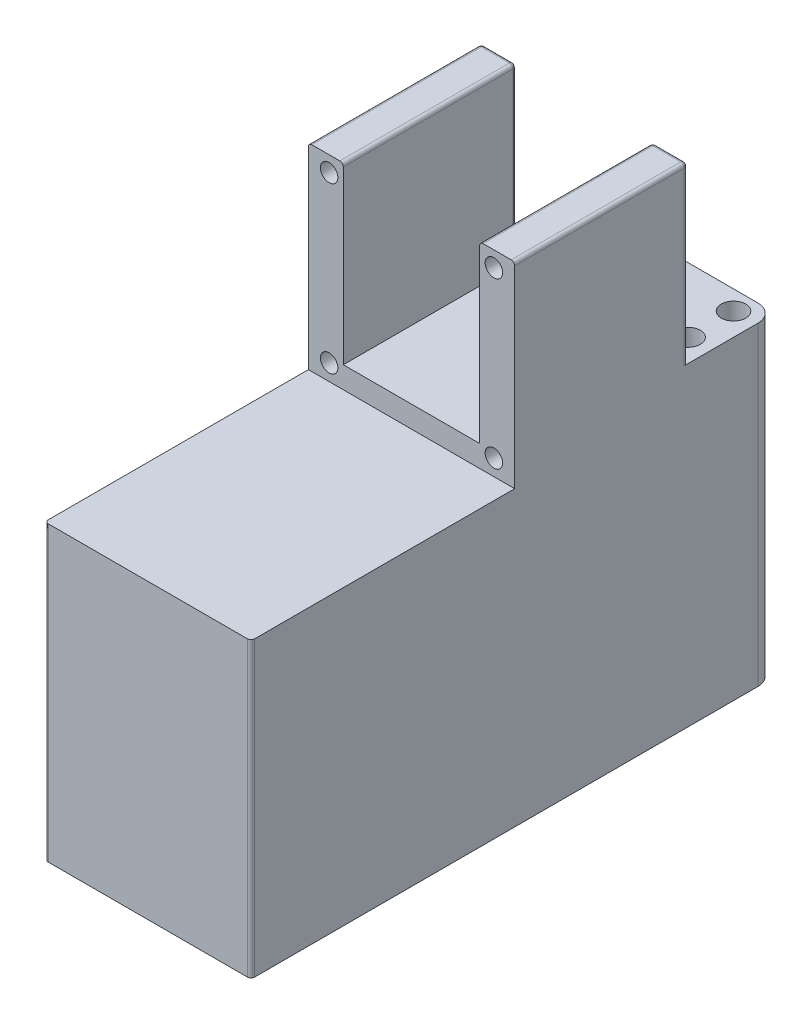
SolidWorks part; units mm, degrees
note: The reader was unsure of these and kept them because the rebuilt part matched: shared geometry of "Sketch6<3>".
ref_plane "Front Plane" through (0, 0, 0) normal (0, 0, 1) x (1, 0, 0)
ref_plane "Top Plane" through (0, 0, 0) normal (0, 1, 0) x (1, 0, 0)
ref_plane "Right Plane" through (0, 0, 0) normal (1, 0, 0) x (0, 0, -1)
sketch "Sketch1" plane through (0, 0, 0) normal (0, 0, 1) x (1, 0, 0)
  line L1 (-29.5, 15) -> (29.5, 15)
  line L2 (-29.5, 15) -> (-29.5, -15)
  line L3 (-29.5, -15) -> (29.5, -15)
  line L4 (29.5, 15) -> (29.5, -15)
  line L5 (-29.5, 15) -> (29.5, -15) construction
  line L6 (-29.5, -15) -> (29.5, 15) construction
  line L90 (4, 2.7272) -> (6.5728, 5.3)
  line L91 (6.5728, 5.3) -> (8, 5.3)
  line L92 (8, 5.3) -> (8, 3.1)
  line L93 (8, 3.1) -> (10, 5.1)
  line L94 (10, 5.1) -> (10, 10)
  line L95 (10, 10) -> (5.1, 10)
  line L96 (5.1, 10) -> (3.1, 8)
  line L97 (3.1, 8) -> (5.3, 8)
  line L98 (5.3, 8) -> (5.3, 6.5728)
  line L99 (5.3, 6.5728) -> (2.7272, 4)
  line L100 (2.7272, 4) -> (-2.7272, 4)
  line L101 (-2.7272, 4) -> (-5.3, 6.5728)
  line L102 (-5.3, 6.5728) -> (-5.3, 8)
  line L103 (-5.3, 8) -> (-3.1, 8)
  line L104 (-3.1, 8) -> (-5.1, 10)
  line L105 (-5.1, 10) -> (-10, 10)
  line L106 (-10, 10) -> (-10, 5.1)
  line L107 (-10, 5.1) -> (-8, 3.1)
  line L108 (-8, 3.1) -> (-8, 5.3)
  line L109 (-8, 5.3) -> (-6.5728, 5.3)
  line L110 (-6.5728, 5.3) -> (-4, 2.7272)
  line L111 (-4, 2.7272) -> (-4, -2.7272)
  line L112 (-4, -2.7272) -> (-6.5728, -5.3)
  line L113 (-6.5728, -5.3) -> (-8, -5.3)
  line L114 (-8, -5.3) -> (-8, -3.1)
  line L115 (-8, -3.1) -> (-10, -5.1)
  line L116 (-10, -5.1) -> (-10, -10)
  line L117 (-10, -10) -> (-5.1, -10)
  line L118 (-5.1, -10) -> (-3.1, -8)
  line L119 (-3.1, -8) -> (-5.3, -8)
  line L120 (-5.3, -8) -> (-5.3, -6.5728)
  line L121 (-5.3, -6.5728) -> (-2.7272, -4)
  line L122 (-2.7272, -4) -> (2.7272, -4)
  line L123 (2.7272, -4) -> (5.3, -6.5728)
  line L124 (5.3, -6.5728) -> (5.3, -8)
  line L125 (5.3, -8) -> (3.1, -8)
  line L126 (3.1, -8) -> (5.1, -10)
  line L127 (5.1, -10) -> (10, -10)
  line L128 (10, -10) -> (10, -5.1)
  line L129 (10, -5.1) -> (8, -3.1)
  line L130 (8, -3.1) -> (8, -5.3)
  line L131 (8, -5.3) -> (6.5728, -5.3)
  line L132 (6.5728, -5.3) -> (4, -2.7272)
  line L133 (4, -2.7272) -> (4, 2.7272)
  point P2 (0, 0)
  dimension "D1" = 20
  dimension "D2" = 59
  dimension "D3" = 30
extrude "Boss-Extrude1" add sketch "Sketch1" against normal blind 30
sketch "Sketch2" plane through (0, 15, 0) normal (0, 1, 0) x (1, 0, 0)
  line L0 (-29.5, 30) -> (-29.5, 0) construction
  circle A0 centre (0, 10) radius 2.5
  circle A1 centre (0, 20) radius 2.5
  circle A2 centre (-23, 24.5) radius 3.5
  circle A4 centre (23, 24.5) radius 3.5
  circle A7 centre (23, 11.5) radius 3.5
  circle A9 centre (-23, 11.5) radius 3.5
  dimension "D1" = 10
  dimension "D3" = 46
  dimension "D2" = 10
  dimension "D4" = 13
  dimension "D5" = 6.5
  dimension "D6" = 5.5
extrude "Cut-Extrude1" cut sketch "Sketch2" against normal through all
sketch "Sketch3" plane through (0, 0, 0) normal (0, 0, 1) x (1, 0, 0)
  line L5 (-29.5, -15) -> (29.5, -15)
  line L7 (-29.5, -15) -> (-29.5, -75)
  line L8 (29.5, -15) -> (29.5, -75)
  line L9 (-29.5, -75) -> (29.5, -75)
  dimension "D4" = 60
extrude "Boss-Extrude2" add sketch "Sketch3" against normal up to surface (30 mm away) up to face at (0, 0, -30)
fillet "Fillet2" radius 5 1 edges at (29.5, -30, -30)
fillet "Fillet3" radius 5 1 edges at (-29.5, -30, -30)
sketch "Sketch5" plane through (0, 0, 0) normal (0, 0, 1) x (1, 0, 0)
  line L0 (-29.5, -75) -> (29.5, -75)
  line L1 (-29.5, -75) -> (-29.5, 15)
  line L2 (29.5, -75) -> (29.5, 15)
  line L3 (-29.5, 15) -> (29.5, 15)
extrude "Boss-Extrude3" add sketch "Sketch5" along normal blind 120
sketch "Sketch6" plane through (-29.5, 0, 0) normal (-1, 0, 0) x (0, 0, 1)
  line L0 (120, 8.8) -> (44.6, 8.8) construction
  line L1 (120, 15) -> (120, -75) construction
  line L2 (44.6, 15) -> (44.6, 8.8) construction
  line L3 (-25, 15) -> (120, 15) construction
  line L5 (44.6, 15) -> (-4.88, 15)
  line L6 (44.6, 15) -> (44.6, 65)
  line L7 (44.6, 65) -> (-4.88, 65)
  line L8 (-4.88, 15) -> (-4.88, 65)
  line L9 (44.6, 15) -> (120, 15)
  line L10 (44.6, 15) -> (44.6, 8.8)
  line L11 (44.6, 8.8) -> (120, 8.8)
  line L12 (120, 15) -> (120, 8.8)
  dimension "D1" = 75.4
  dimension "D2" = 6.2
  dimension "D3" = 49.48
  dimension "D4" = 50
extrude "Cut-Extrude2" cut sketch "Sketch6" against normal blind 120 contours L10 L11 L12 L9
extrude "Boss-Extrude4" add sketch "Sketch6<3>" against normal blind 10 contours L6 L7 L8 L5
sketch "Sketch6<3>" plane through (-29.5, 0, 0) normal (-1, 0, 0) x (0, 0, 1) same geometry as "Sketch6"
sketch "Sketch11" plane through (0, 0, 44.6) normal (0, 0, 1) x (1, 0, 0)
  line L0 (-23.56, 65) -> (-23.56, 8.8) construction
  line L1 (29.5, 8.8) -> (-29.5, 8.8) construction
  line L2 (-29.5, 65) -> (-29.5, 8.8) construction
  circle A0 centre (-23.56, 60.57) radius 2.5
  circle A1 centre (-23.56, 13.43) radius 2.5
  dimension "D1" = 4.43
  dimension "D2" = 5.94
  dimension "D3" = 47.14
hole_wizard "Ø5.0 (5) Diameter Hole1" positions "Sketch12" profile "Sketch13" hole size "Ø5.0" standard "ANSI Metric"
sketch "Sketch12" plane through (0, 0, 44.6) normal (0, 0, 1) x (1, 0, 0)
  point P0 (-23.56, 60.57)
sketch "Sketch13" plane through (-23.56, 60.57, 44.6) normal (1, 0, 0) x (0, -1, 0)
  line L0 (0, 0) -> (0, 20)
  line L1 (0, 20) -> (2.5, 18.4978)
  line L2 (2.5, 18.4978) -> (2.5, 0)
  line L5 (2.5, 0) -> (0, 0)
  line L10 (0, 20) -> (-2.5, 18.4978) construction
  line L11 (0, -6.35) -> (0, 107.95) construction
  dimension "Hole Dia." = 5
  dimension "Hole Depth" = 20
  dimension "Drill Angle" = 118
sketch "Sketch14" plane through (29.5, 0, 0) normal (1, 0, 0) x (0, 0, -1)
  line L5 (4.88, 15) -> (-44.6, 15)
  line L6 (4.88, 15) -> (4.88, 65)
  line L7 (4.88, 65) -> (-44.6, 65)
  line L8 (-44.6, 15) -> (-44.6, 65)
  dimension "D3" = 49.48
  dimension "D4" = 50
extrude "Boss-Extrude6" add sketch "Sketch14" against normal blind 10
sketch "Sketch15" plane through (0, 0, 44.6) normal (0, 0, 1) x (1, 0, 0)
  line L0 (23.56, 65) -> (23.56, 8.8) construction
  line L1 (29.5, 8.8) -> (-29.5, 8.8) construction
  line L2 (-29.5, 65) -> (-29.5, 8.8) construction
  line L3 (29.5, 8.8) -> (29.5, 65) construction
  circle A0 centre (23.56, 60.57) radius 2.5
  circle A1 centre (23.56, 13.43) radius 2.5
  dimension "D1" = 4.43
  dimension "D3" = 47.14
  dimension "D2" = 5.94
hole_wizard "Ø5.0 (5) Diameter Hole2" positions "Sketch16" profile "Sketch17" hole size "Ø5.0" standard "ANSI Metric"
sketch "Sketch16" plane through (0, 0, 44.6) normal (0, 0, 1) x (1, 0, 0)
  point P0 (23.56, 60.57)
sketch "Sketch17" plane through (23.56, 60.57, 44.6) normal (1, 0, 0) x (0, -1, 0)
  line L0 (0, 0) -> (0, 20)
  line L1 (0, 20) -> (2.5, 18.4978)
  line L2 (2.5, 18.4978) -> (2.5, 0)
  line L5 (2.5, 0) -> (0, 0)
  line L10 (0, 20) -> (-2.5, 18.4978) construction
  line L11 (0, -6.35) -> (0, 107.95) construction
  dimension "Hole Dia." = 5
  dimension "Hole Depth" = 20
  dimension "Drill Angle" = 118
fillet "Fillet4" radius 1 1 edges at (-29.5, 40, -4.88)
fillet "Fillet5" radius 1 1 edges at (-19.5, 40, -4.88)
fillet "Fillet6" radius 1 1 edges at (29.5, 40, -4.88)
fillet "Fillet7" radius 1 1 edges at (19.5, 40, -4.88)
fillet "Fillet8" radius 1 5 edges at (-19.5, 65, 20.36) (-29.5, 65, 20.36) (-29.2071, 65, -4.5871) (-24.5, 65, -4.88) (-19.7929, 65, -4.5871)
fillet "Fillet9" radius 1 5 edges at (29.5, 65, 20.36) (29.2071, 65, -4.5871) (19.5, 65, 20.36) (24.5, 65, -4.88) (19.7929, 65, -4.5871)
fillet "Fillet10" radius 1 1 edges at (29.5, -33.1, 120)
fillet "Fillet11" radius 1 1 edges at (-29.5, -33.1, 120)
hole_wizard "Ø5.0 (5) Diameter Hole3" positions "Sketch18" profile "Sketch19" hole size "Ø5.0" standard "ANSI Metric"
sketch "Sketch18" plane through (0, 0, 44.6) normal (0, 0, 1) x (1, 0, 0)
  point P0 (-23.56, 13.43)
  point P3 (23.56, 13.43)
sketch "Sketch19" plane through (-23.56, 13.43, 44.6) normal (1, 0, 0) x (0, -1, 0)
  line L0 (0, 0) -> (0, 20)
  line L1 (0, 20) -> (2.5, 18.4978)
  line L2 (2.5, 18.4978) -> (2.5, 0)
  line L5 (2.5, 0) -> (0, 0)
  line L10 (0, 20) -> (-2.5, 18.4978) construction
  line L11 (0, -6.35) -> (0, 107.95) construction
  dimension "Hole Dia." = 5
  dimension "Hole Depth" = 20
  dimension "Drill Angle" = 118
sketch "Sketch20" plane through (0, 0, 0) normal (0, 1, 0) x (1, 0, 0)
  line L4 (-28.5, -120) -> (28.5, -120)
  line L5 (-29.5, 25) -> (-29.5, -119)
  line L6 (24.5, 30) -> (-24.5, 30)
  line L7 (29.5, -119) -> (29.5, 25)
  line L8 (-28.5, -120) -> (28.5, -120)
  line L9 (-29.5, 25) -> (-29.5, -119)
  line L10 (24.5, 30) -> (-24.5, 30)
  line L11 (29.5, -119) -> (29.5, 25)
  arc A4 (-29.5, -119) -> (-28.5, -120) centre (-28.5, -119) ccw
  arc A5 (-24.5, 30) -> (-29.5, 25) centre (-24.5, 25) ccw
  arc A6 (29.5, 25) -> (24.5, 30) centre (24.5, 25) ccw
  arc A7 (28.5, -120) -> (29.5, -119) centre (28.5, -119) ccw
  arc A8 (-29.5, -119) -> (-28.5, -120) centre (-28.5, -119) ccw
  arc A9 (-24.5, 30) -> (-29.5, 25) centre (-24.5, 25) ccw
  arc A10 (29.5, 25) -> (24.5, 30) centre (24.5, 25) ccw
  arc A11 (28.5, -120) -> (29.5, -119) centre (28.5, -119) ccw
  dimension "D1" = 0
sketch "Sketch21" plane through (0, 0, 0) normal (0, 1, 0) x (1, 0, 0)
  line L0 (0, -120) -> (0, 30) construction
  line L1 (-28.5, -120) -> (28.5, -120) construction
  line L2 (24.5, 30) -> (-24.5, 30) construction
  circle A0 centre (0, -70.33) radius 2.35
  circle A1 centre (0, -20.66) radius 2.35
  dimension "D3" = 4.7
  dimension "D4" = 4.7
  dimension "D1" = 49.67
  dimension "D2" = 49.67
extrude "Cut-Extrude3" cut sketch "Sketch21" along normal blind 20 from surface at -75 starting at face at (0, -75, 45.7929)
